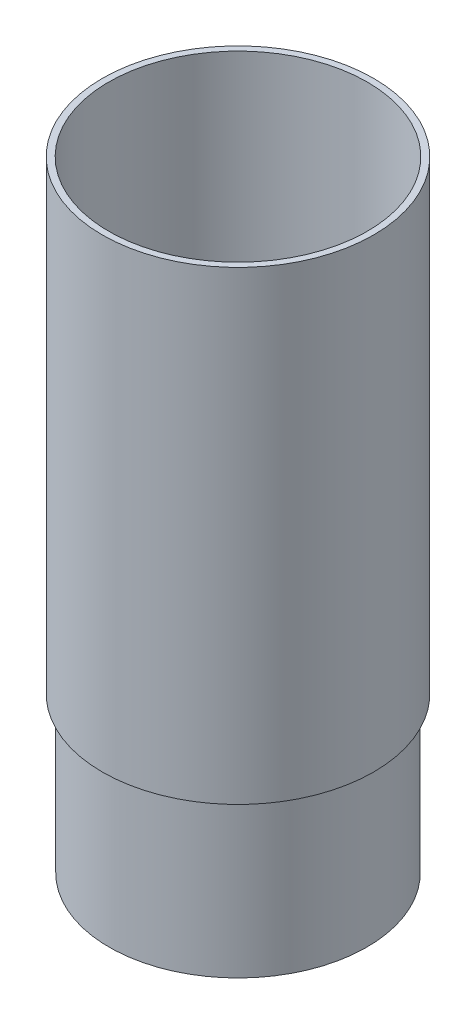
SolidWorks part; units mm, degrees
material "ABS"
ref_plane "Front Plane" through (0, 0, 0) normal (0, 0, 1) x (1, 0, 0)
ref_plane "Top Plane" through (0, 0, 0) normal (0, 1, 0) x (1, 0, 0)
ref_plane "Right Plane" through (0, 0, 0) normal (1, 0, 0) x (0, 0, -1)
sketch "Sketch1" plane through (0, 0, 0) normal (0, 0, 1) x (1, 0, 0)
  line L0 (0, 0) -> (0, 54.0332) construction
  line L1 (-20.0787, 0) -> (-20.0787, 27.3)
  line L2 (-20.0787, 27.3) -> (-21.1836, 31.4235)
  line L3 (-21.1836, 31.4235) -> (-21.1836, 101.6)
  line L4 (-21.1836, 101.6) -> (-22.225, 101.6)
  line L5 (-22.225, 101.6) -> (-22.225, 25.4)
  line L6 (-22.225, 25.4) -> (-21.1201, 25.4)
  line L7 (-21.1201, 25.4) -> (-21.1201, 0)
  line L8 (-21.1201, 0) -> (-20.0787, 0)
  point P5 (0, 0)
  dimension "D1" = 42.2402
  dimension "D2" = 44.45
  dimension "D3" = 25.4
  dimension "D4" = 101.6
  dimension "D5" = 1.0414
  dimension "D6" = 1.0414
  dimension "D7" = 15
  dimension "D8" = 1.9
revolve "Revolve1" add sketch "Sketch1" angle 360 mid plane about L0
